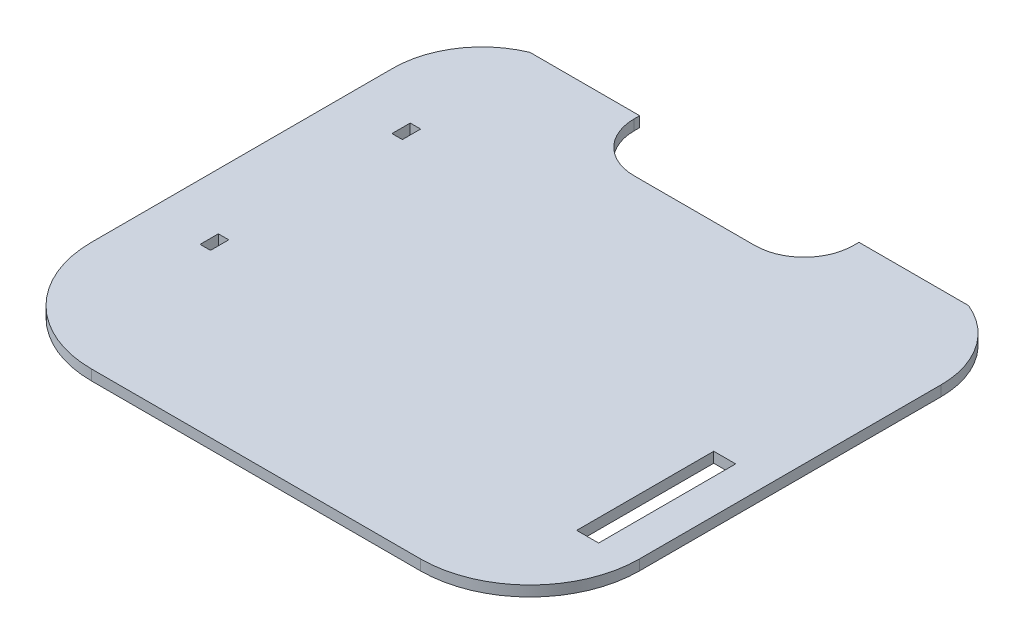
SolidWorks part; units mm, degrees
ref_plane "Front Plane" through (0, 0, 0) normal (0, 0, 1) x (1, 0, 0)
ref_plane "Top Plane" through (0, 0, 0) normal (0, 1, 0) x (1, 0, 0)
ref_plane "Right Plane" through (0, 0, 0) normal (1, 0, 0) x (0, 0, -1)
sketch "Sketch1" plane through (0, 0, 0) normal (0, 1, 0) x (1, 0, 0)
  line L1 (-127, 114.3) -> (127, 114.3)
  line L2 (-127, 114.3) -> (-127, -114.3)
  line L3 (-127, -114.3) -> (127, -114.3)
  line L4 (127, 114.3) -> (127, -114.3)
  line L5 (-127, 114.3) -> (127, -114.3) construction
  line L6 (-127, -114.3) -> (127, 114.3) construction
  point P0 (0, 0)
  dimension "D1" = 254
  dimension "D2" = 228.6
extrude "Boss-Extrude1" add sketch "Sketch1" along normal blind 4.826
sketch "Sketch4" plane through (0, 4.826, 0) normal (0, 1, 0) x (1, 0, 0)
  line L0 (0, -114.3) -> (0, 114.3) construction
  line L1 (-127, -114.3) -> (127, -114.3) construction
  line L2 (127, 114.3) -> (-127, 114.3) construction
  line L3 (-127, 76.2) -> (-101.6, 76.2) construction
  line L4 (-127, 114.3) -> (-127, -114.3) construction
  line L5 (-101.6, 76.2) -> (-101.6, 114.3) construction
  line L6 (-127, 76.2) -> (-127, 114.3)
  line L7 (-127, 114.3) -> (-101.6, 114.3)
  line L8 (127, 76.2) -> (127, 114.3)
  line L9 (127, 114.3) -> (101.6, 114.3)
  arc A0 (-127, 76.2) -> (-101.6, 114.3) centre (-85.725, 76.2) cw
  arc A1 (127, 76.2) -> (101.6, 114.3) centre (85.725, 76.2) ccw
  dimension "D2" = 38.1
extrude "Cut-Extrude3" cut sketch "Sketch4" against normal blind 4.826
sketch "Sketch7" plane through (0, 4.826, 0) normal (0, 1, 0) x (1, 0, 0)
  line L0 (0, -114.3) -> (0, 114.3) construction
  line L1 (-127, -114.3) -> (127, -114.3) construction
  line L2 (101.6, 114.3) -> (-101.6, 114.3) construction
  line L3 (50.8, 88.9) -> (50.8, 114.3)
  line L4 (50.8, 88.9) -> (-50.8, 88.9)
  line L5 (0, 88.9) -> (0, 114.3)
  line L6 (50.8, 114.3) -> (-50.8, 114.3)
  line L7 (-50.8, 88.9) -> (-50.8, 114.3)
  line M6 (101.6, 114.3) -> (-101.6, 114.3)
extrude "Cut-Extrude5" cut sketch "Sketch7" against normal blind 4.826 contours L7 L4 L5 M6 | L5 L4 L3 M6 region at (25.4, 4.826, -101.6) region at (-25.4, 4.826, -101.6)
fillet "Fillet9" radius 22.86 1 edges at (-50.8, 2.413, -88.9) type face fillet first side face at (0, 2.413, -88.9) second side face at (-50.8, 2.413, -101.6)
fillet "Fillet10" radius 22.86 1 edges at (50.8, 2.413, -88.9) type face fillet first side face at (11.43, 2.413, -88.9) second side face at (50.8, 2.413, -101.6)
sketch "Sketch19" plane through (0, 4.826, 0) normal (0, 1, 0) x (1, 0, 0)
  line L0 (-101, -39.1583) -> (-101, -30.6917) construction
  line L1 (-101, -39.1583) -> (-96.174, -39.1583) construction
  line L2 (-96.174, -39.1583) -> (-96.174, -30.6917) construction
  line L3 (-101, -30.6917) -> (-96.174, -30.6917) construction
  line L4 (-101, 49.7417) -> (-101, 58.2083) construction
  line L5 (-101, 49.7417) -> (-96.174, 49.7417) construction
  line L6 (-96.174, 49.7417) -> (-96.174, 58.2083) construction
  line L7 (-101, 58.2083) -> (-96.174, 58.2083) construction
  line L8 (-101, -39.1583) -> (-101, -30.6917)
  line L9 (-101, -39.1583) -> (-96.174, -39.1583)
  line L10 (-96.174, -39.1583) -> (-96.174, -30.6917)
  line L11 (-101, -30.6917) -> (-96.174, -30.6917)
  line L12 (-101, 49.7417) -> (-101, 58.2083)
  line L13 (-101, 49.7417) -> (-96.174, 49.7417)
  line L14 (-96.174, 49.7417) -> (-96.174, 58.2083)
  line L15 (-101, 58.2083) -> (-96.174, 58.2083)
extrude "Cut-Extrude16" cut sketch "Sketch19" against normal through all
fillet "Fillet11" radius 50.8 2 edges at (-127, 2.413, 114.3) (127, 2.413, 114.3)
sketch "Sketch20" plane through (0, 0, 0) normal (0, -1, 0) x (1, 0, 0)
  line L1 (101, 66.675) -> (111.16, 66.675)
  line L2 (101, 66.675) -> (101, 3.175)
  line L3 (101, 3.175) -> (111.16, 3.175)
  line L4 (111.16, 66.675) -> (111.16, 3.175)
  dimension "D1" = 10.16
extrude "Cut-Extrude17" cut sketch "Sketch20" against normal through all
equation "\"MDF\"= 0.19in"
equation "\"GenDiameter\"= 60mm"
equation "\"GenCutDiameter\" = 1.8in"
equation "\"GenCutDistance\" = 1"
equation "\"TowerHeight\" = 6in"
equation "\"TowerFrontBase\" = 3in"
equation "\"FunnelHeight\" = 1in"
equation "\"FunnelAngle\" = 20"
equation "\"TowerSideBase\" = 3in"
equation "\"BaseLength\" = 9in"
equation "\"BaseWidth\" = 10in"
equation "\"WheelHoleLength\" = 3.25in"
equation "\"WheelHoleWidth\" = 26mm"
equation "\"DropLength\" = 1in"
equation "\"D1@Sketch1\"=\"BaseWidth\""
equation "\"D2@Sketch1\"=\"BaseLength\""
equation "\"D1@Boss-Extrude1\"=\"MDF\""
equation "\"WheelHoleFromBack\" = 1.5in"
equation "\"DropWidth\" = 8.5in"
equation "\"BumperWidth\" = 1in"
equation "\"D1@Sketch4\"=\"BumperWidth\""
equation "\"D2@Sketch4\"=\"WheelHoleFromBack\""
equation "\"D1@Cut-Extrude3\"=\"MDF\""
equation "\"D1@Sketch7\"=\"DropLength\""
equation "\"D2@Sketch7\"=\"DropWidthTop\"/2"
equation "\"D1@Cut-Extrude5\"=\"MDF\""
equation "\"DropWidthTop\" = 4in"
